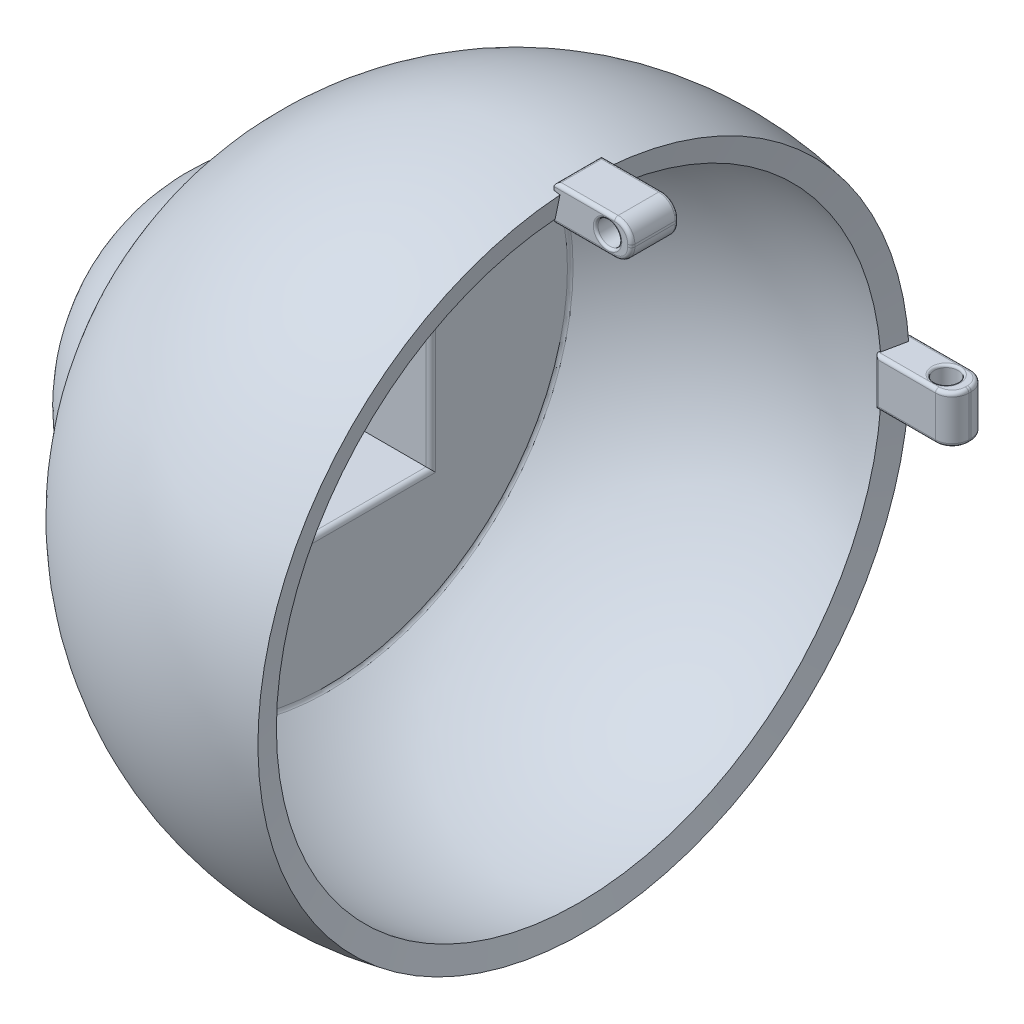
SolidWorks part; units mm, degrees
ref_plane "Front Plane" through (0, 0, 0) normal (0, 0, 1) x (1, 0, 0)
ref_plane "Top Plane" through (0, 0, 0) normal (0, 1, 0) x (1, 0, 0)
ref_plane "Right Plane" through (0, 0, 0) normal (1, 0, 0) x (0, 0, -1)
sketch "Sketch2" plane through (0, 0, 0) normal (0, 0, 1) x (1, 0, 0)
  line L0 (0, 0) -> (2.8342, 13.7101)
  line L1 (2.8342, 13.7101) -> (2.8342, 0) construction
  line L2 (-14.7764, 14) -> (9.8368, 14) construction
  line L3 (55, 0) -> (-55, 0) construction
  line L5 (0, 0) -> (-16.1658, 0)
  line L7 (0, 0) -> (2.8342, 0) construction
  arc A0 (-12.1244, 7) -> (2.8342, 13.7101) centre (0, 0) cw
  arc A1 (-16.1658, 0) -> (-12.1244, 7) centre (-8.0829, 0) cw
  point P2 (0, 0)
  point P4 (-8.0829, 0)
  dimension "D1" = 14
  dimension "D2" = 19
  dimension "D4" = 7
  dimension "D5" = 14
  dimension "D3" = 2.8342
  dimension "D6" = 78.32
ref_axis "Axis1" through (-17.2484, 0, 0) along (1, 0, 0)
revolve "Revolve1" add sketch "Sketch2" angle 360 about L5
shell "Shell3" thickness 1 removed face at (2.8342, 13.7101, 0)
sketch "Sketch3" plane through (0, 0, 0) normal (1, 0, 0) x (0, 0, -1)
  circle A0 centre (0, 0) radius 4.25
extrude "Cut-Extrude2" cut sketch "Sketch3" against normal blind 71 from offset 0
ref_plane "Plane4" through (-12, 0, 0) normal (1, 0, 0) x (0, 0, -1)
sketch "Sketch6" plane through (-12, 0, 0) normal (1, 0, 0) x (0, 0, -1)
  line L1 (-4.4, 4.4559) -> (4.4, 4.4559)
  line L2 (-4.4, 4.4559) -> (-4.4, -4.4559)
  line L3 (-4.4, -4.4559) -> (4.4, -4.4559)
  line L4 (4.4, 4.4559) -> (4.4, -4.4559)
  line L5 (-4.4, 4.4559) -> (4.4, -4.4559) construction
  line L6 (-4.4, -4.4559) -> (4.4, 4.4559) construction
  circle A0 centre (0, 0) radius 6.2622 construction
  point P0 (0, 0)
  dimension "D1" = 8.8
extrude "Extrude-Thin1" add sketch "Sketch6" against normal up to surface and the other way blind 4 thin up to face at (-13.749, 0, -4.25) thin type one direction wall 0.5
ref_plane "Plane5" through (-11.3923, 0, 0) normal (1, 0, 0) x (0, 0, -1)
sketch "Sketch8" plane through (-11.3923, 0, 0) normal (1, 0, 0) x (0, 0, -1)
  line L1 (-4.4, 4.4559) -> (4.4, 4.4559)
  line L2 (-4.4, 4.4559) -> (-4.4, -4.4559)
  line L3 (-4.4, -4.4559) -> (4.4, -4.4559)
  line L4 (4.4, 4.4559) -> (4.4, -4.4559)
  circle A0 centre (0, 0) radius 4.25
  dimension "D1" = 8.5
extrude "Boss-Extrude5" add sketch "Sketch8" against normal up to surface up to face at (-13.749, 0, -4.25)
sketch "Sketch12" plane through (0, 4.9559, 0) normal (0, 1, 0) x (1, 0, 0)
  line L3 (-10.974, -4.9) -> (-8, -4.9)
  line L4 (-8, -4.9) -> (-8, 4.9)
  line L5 (-8, 4.9) -> (-10.974, 4.9)
  line L6 (-10.974, -4.9) -> (-8, -4.9)
  line L7 (-8, -4.9) -> (-8, 4.9)
  line L8 (-8, 4.9) -> (-10.974, 4.9)
  arc A3 (-11.3923, 3.8281) -> (-11.3923, -3.8281) centre (-8.0829, 0) ccw
  arc A4 (-11.3923, -3.8281) -> (-10.974, -4.9) centre (0, 0) ccw
  arc A5 (-10.974, 4.9) -> (-11.3923, 3.8281) centre (0, 0) ccw
  arc A6 (-11.3923, 3.8281) -> (-11.3923, -3.8281) centre (-8.0829, 0) ccw
  arc A7 (-11.3923, -3.8281) -> (-10.974, -4.9) centre (0, 0) ccw
  arc A8 (-10.974, 4.9) -> (-11.3923, 3.8281) centre (0, 0) ccw
  dimension "D1" = 0
extrude "Boss-Extrude7" add sketch "Sketch12" along normal up to surface (4.0435 mm away) up to face at (2.6318, -12.7308, 0)
sketch "Sketch13" plane through (0, -4.9559, 0) normal (0, -1, 0) x (1, 0, 0)
  line L3 (-10.974, -4.9) -> (-8, -4.9)
  line L4 (-8, -4.9) -> (-8, 4.9)
  line L5 (-8, 4.9) -> (-10.974, 4.9)
  line L6 (-10.974, -4.9) -> (-8, -4.9)
  line L7 (-8, -4.9) -> (-8, 4.9)
  line L8 (-8, 4.9) -> (-10.974, 4.9)
  arc A3 (-11.3923, 3.8281) -> (-11.3923, -3.8281) centre (-8.0829, 0) ccw
  arc A4 (-11.3923, -3.8281) -> (-10.974, -4.9) centre (0, 0) ccw
  arc A5 (-10.974, 4.9) -> (-11.3923, 3.8281) centre (0, 0) ccw
  arc A6 (-11.3923, 3.8281) -> (-11.3923, -3.8281) centre (-8.0829, 0) ccw
  arc A7 (-11.3923, -3.8281) -> (-10.974, -4.9) centre (0, 0) ccw
  arc A8 (-10.974, 4.9) -> (-11.3923, 3.8281) centre (0, 0) ccw
  dimension "D1" = 0
extrude "Boss-Extrude8" add sketch "Sketch13" along normal up to surface (4.0435 mm away) contours A6 A7 L6 L7 L8 A8 up to face at (2.6318, -12.7308, 0)
sketch "Sketch14" plane through (0, 0, 4.9) normal (0, 0, 1) x (1, 0, 0)
  line L1 (-8, -8.9994) -> (-8, 8.9994)
  line L2 (-8, -8.9994) -> (-8, 8.9994)
  arc A3 (-11.3923, 3.8994) -> (-11.3923, -3.8994) centre (-8.0829, 0) ccw
  arc A4 (-11.3923, -3.8994) -> (-8, -8.9994) centre (0, 0) ccw
  arc A5 (-8, 8.9994) -> (-11.3923, 3.8994) centre (0, 0) ccw
  arc A6 (-11.3923, 3.8994) -> (-11.3923, -3.8994) centre (-8.0829, 0) ccw
  arc A7 (-11.3923, -3.8994) -> (-8, -8.9994) centre (0, 0) ccw
  arc A8 (-8, 8.9994) -> (-11.3923, 3.8994) centre (0, 0) ccw
  dimension "D1" = 0
extrude "Boss-Extrude9" add sketch "Sketch14" along normal up to surface up to face at (2.6318, -12.7308, 0)
sketch "Sketch15" plane through (0, 0, -4.9) normal (0, 0, -1) x (-1, 0, 0)
  line L1 (8, 8.9994) -> (8, -8.9994)
  line L2 (8, 8.9994) -> (8, -8.9994)
  arc A3 (8, -8.9994) -> (11.3923, -3.8994) centre (0, 0) ccw
  arc A4 (11.3923, -3.8994) -> (11.3923, 3.8994) centre (8.0829, 0) ccw
  arc A5 (11.3923, 3.8994) -> (8, 8.9994) centre (0, 0) ccw
  arc A6 (8, -8.9994) -> (11.3923, -3.8994) centre (0, 0) ccw
  arc A7 (11.3923, -3.8994) -> (11.3923, 3.8994) centre (8.0829, 0) ccw
  arc A8 (11.3923, 3.8994) -> (8, 8.9994) centre (0, 0) ccw
  dimension "D1" = 0
extrude "Boss-Extrude10" add sketch "Sketch15" along normal up to surface up to face at (2.6318, -12.7308, 0)
ref_plane "Plane6" through (0, 0, -14) normal (0, 0, -1) x (-1, 0, 0)
sketch "Sketch16" plane through (0, 0, -14) normal (0, 0, -1) x (-1, 0, 0)
  line L0 (-2.8342, 13.7101) -> (-2.8342, -13.7101) construction
  line L1 (-5.8342, 1) -> (-2.8342, 1)
  line L2 (-5.8342, 1) -> (-5.8342, -1)
  line L3 (-5.8342, -1) -> (-2.8342, -1)
  line L4 (-2.8342, 1) -> (-2.8342, -1) construction
  line L5 (17.2484, 0) -> (-3.6516, 0) construction
  line L6 (-2.8342, -1) -> (-5.8342, 1) construction
  line L7 (-4.3342, 0) -> (-5.8342, 0) construction
  line L8 (-2.8342, 1) -> (-2.5842, 1)
  line L9 (-2.5842, 1) -> (-2.5842, -1)
  line L10 (-2.5842, -1) -> (-2.8342, -1)
  point P9 (-2.8342, 0)
  dimension "D1" = 3
  dimension "D2" = 2
  dimension "D3" = 0.25
extrude "Boss-Extrude11" add sketch "Sketch16" against normal blind 1.5 separate body
sketch "Sketch17" plane through (0, -1, 0) normal (0, -1, 0) x (1, 0, 0)
  line L0 (4.8342, -12.5) -> (4.8342, -14) construction
  line L4 (5.8342, -12.5) -> (2.5842, -12.5) construction
  line L5 (-9.6678, -14) -> (9.6678, -14) construction
  line L6 (5.8342, -12.5) -> (5.8342, -14) construction
  circle A0 centre (4.8342, -13.25) radius 0.5
  point P8 (4.8342, -13.25)
  point P10 (0, 0)
  dimension "D1" = 1
  dimension "D2" = 1
extrude "Cut-Extrude3" cut sketch "Sketch17" against normal blind 2
fillet "Fillet1" radius 0.7 2 edges at (5.8342, 0, -12.5) (5.8342, 0, -14)
fillet "Fillet2" radius 0.15 12 edges at (3.8592, 1, -14) (5.6292, 1, -13.795) (5.6292, 1, -12.705) (3.8592, 1, -12.5) (3.8592, -1, -12.5) (5.6292, -1, -12.705) (5.6292, -1, -13.795) (3.8592, -1, -14) (5.8342, -1, -13.25) (5.8342, 1, -13.25) (2.5842, 0, -12.5) (2.5842, 0, -14)
fillet "Fillet3" radius 0.1 2 edges at (5.3342, 1, -13.25) (5.3342, -1, -13.25)
pattern_circular "CirPattern4" count 2 every 90 about axis through (-17.2484, 0, 0) along (1, 0, 0) of bodies 131
fillet "Fillet6" radius 0.2 5 edges at (-8, 0, 4.4) (-8, -4.4559, 0) (-8, 0, -4.4) (-8, 4.4559, 0) (-8, 0, 10.247)
fillet "Fillet7" radius 0.2 2 edges at (-14.9583, 0, -4.25) (-11.3923, 0, -4.25)
fillet "Fillet8" radius 0.4 1 edges at (-12.1244, 7, 0)
